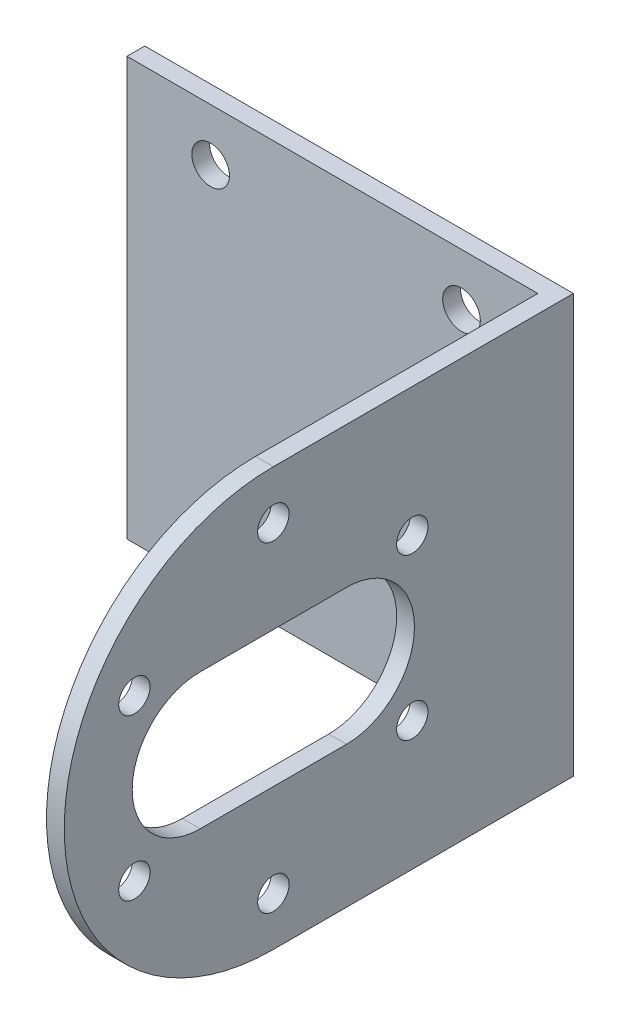
SolidWorks part; units mm, degrees
ref_plane "Alzado" through (0, 0, 0) normal (0, 0, 1) x (1, 0, 0)
ref_plane "Planta" through (0, 0, 0) normal (0, 1, 0) x (1, 0, 0)
ref_plane "Vista lateral" through (0, 0, 0) normal (1, 0, 0) x (0, 0, -1)
sketch "Croquis1" plane through (0, 0, 0) normal (0, 0, 1) x (1, 0, 0)
  line L0 (0, 0) -> (8, 0)
  line L2 (0, 0) -> (0, 40)
  line L4 (41, 0) -> (41, 40)
  line L6 (0, 40) -> (8, 40)
  line L8 (8, 40) -> (41, 40)
  line L9 (41, 0) -> (8, 0)
  circle A0 centre (8, 5) radius 1.8
  circle A1 centre (8, 35) radius 1.8
  circle A2 centre (32, 5) radius 1.8
  circle A3 centre (32, 35) radius 1.8
extrude "Saliente-Extruir1" add sketch "Croquis1" along normal blind 1.7
sketch "Croquis2" plane through (0, 0, 1.7) normal (0, 0, 1) x (1, 0, 0)
  line L0 (41, 40) -> (39.3, 40)
  line L1 (41, 40) -> (0, 40) construction
  line L2 (41, 0) -> (39.3, 0)
  line L3 (0, 0) -> (41, 0) construction
  line L4 (39.3, 0) -> (39.3, 40)
  line L5 (41, 40) -> (41, 0)
extrude "Saliente-Extruir2" add sketch "Croquis2" along normal blind 60
sketch "Croquis3" plane through (39.3, 0, 0) normal (-1, 0, 0) x (0, 0, 1)
  line L0 (28.7, 40) -> (61.7, 40)
  line L2 (61.7, 40) -> (61.7, 0)
  line L3 (21.7, 26.5) -> (35.7, 26.5)
  line L4 (21.7, 13.5) -> (35.7, 13.5)
  line L5 (1.7, 40) -> (28.7, 40)
  line L7 (1.7, 0) -> (28.7, 0)
  line L9 (61.7, 0) -> (28.7, 0)
  arc A0 (21.7, 13.5) -> (21.7, 26.5) centre (21.7, 20) cw
  arc A1 (35.7, 13.5) -> (35.7, 26.5) centre (35.7, 20) ccw
  arc A2 (28.7, 0) -> (28.7, 40) centre (28.7, 20) ccw
  circle A3 centre (41.9935, 27.675) radius 1.5
  circle A4 centre (41.9935, 12.325) radius 1.5
  circle A5 centre (28.7, 35.35) radius 1.5
  circle A6 centre (28.7, 4.65) radius 1.5
  circle A7 centre (15.4065, 27.675) radius 1.5
  circle A8 centre (15.4065, 12.325) radius 1.5
  line M15 (1.7, 0) -> (61.7, 0)
  line M16 (61.7, 0) -> (61.7, 40)
  line M17 (61.7, 40) -> (1.7, 40)
extrude "Cortar-Extruir1" cut sketch "Croquis3" against normal blind 10 contours A2 M15 M16 M17 | L4 A1 L3 A0 region at (39.3, 20, 52.4778) region at (39.3, 20, 28.7)
extrude "Cortar-Extruir2" cut sketch "Croquis3<4>" against normal blind 10 contours A7 | A5 | A3 | A4 | A6 | A8 region at (39.3, 27.675, 41.9935) region at (39.3, 12.325, 41.9935) region at (39.3, 35.35, 28.7) region at (39.3, 4.65, 28.7) region at (39.3, 27.675, 15.4065) region at (39.3, 12.325, 15.4065)
sketch "Croquis3<4>" plane through (39.3, 0, 0) normal (-1, 0, 0) x (0, 0, 1) same geometry as "Croquis3"
